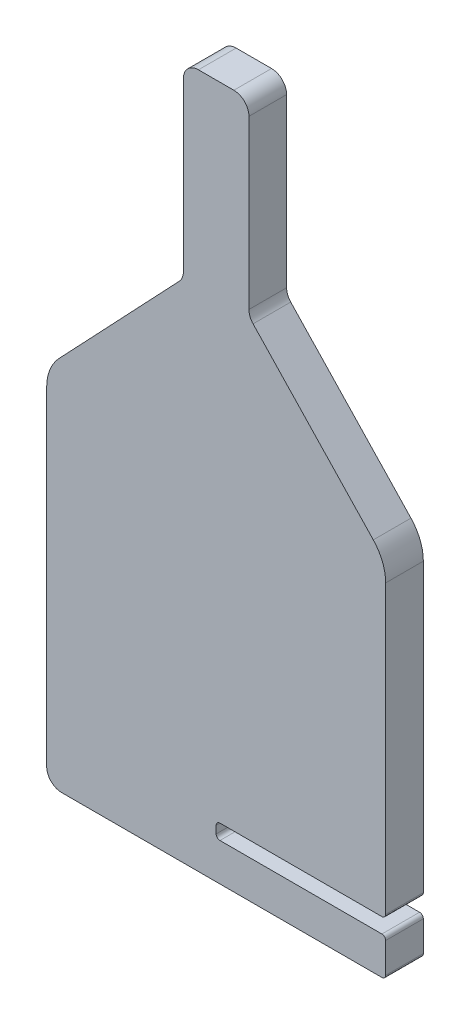
SolidWorks part; units mm, degrees
ref_plane "Alzado" through (0, 0, 0) normal (0, 0, 1) x (1, 0, 0)
ref_plane "Planta" through (0, 0, 0) normal (0, 1, 0) x (1, 0, 0)
ref_plane "Vista lateral" through (0, 0, 0) normal (1, 0, 0) x (0, 0, -1)
sketch "Croquis1" plane through (0, 0, 0) normal (0, 0, 1) x (1, 0, 0)
  line L0 (-4.35, 20) -> (-22.5, 0.8287)
  line L1 (-4.35, 45) -> (4.35, 45)
  line L2 (-22.5, 0.8287) -> (-22.5, -47.1713)
  line L3 (-22.5, -47.1713) -> (22.5, -47.1713)
  line L4 (22.5, 0.8287) -> (22.5, -47.1713)
  line L5 (-4.35, 45) -> (4.35, 45)
  line L6 (-4.35, 45) -> (-4.35, 20)
  line L8 (4.35, 45) -> (4.35, 19.999)
  line L9 (4.35, 19.999) -> (22.5, 0.8287)
  line L10 (0, 72.8664) -> (0, -82.626) construction
  dimension "D1" = 45
  dimension "D2" = 25
  dimension "D3" = 4.35
  dimension "D4" = 22.5
  dimension "D5" = 45
  dimension "D6" = 4.35
  dimension "D7" = 26.3993
  dimension "D8" = 26.4
  dimension "D9" = 48
  dimension "D10" = 48
extrude "Saliente-Extruir1" add sketch "Croquis1" along normal blind 5 contours L6 L0 L2 L3 L4 L9 L8 L1
sketch "Croquis3" plane through (0, 0, 5) normal (0, 0, 1) x (1, 0, 0)
  line L0 (22.5, 0.8287) -> (22.5, -47.1713) construction
  line L1 (22.5, -40.1713) -> (0, -40.1713)
  line L2 (22.5, -40.1713) -> (22.5, -42.1713)
  line L3 (22.5, -42.1713) -> (0, -42.1713)
  line L4 (0, -40.1713) -> (0, -42.1713)
  line L5 (-22.5, -47.1713) -> (22.5, -47.1713) construction
  dimension "D1" = 2
  dimension "D2" = 5
  dimension "D3" = 22.5
extrude "Cortar-Extruir2" cut sketch "Croquis3" against normal up to surface (5 mm away) up to face at (0, 4.6642, 0)
fillet "Redondeo1" radius 2 5 edges at (-22.5, -47.1713, 2.5) (-4.35, 20, 2.5) (-4.35, 45, 2.5) (4.35, 19.999, 2.5) (4.35, 45, 2.5)
fillet "Redondeo2" radius 6 2 edges at (-22.5, 0.8287, 2.5) (22.5, 0.8287, 2.5)
fillet "Redondeo3" radius 0.5 5 edges at (0, -42.1713, 2.5) (0, -40.1713, 2.5) (22.5, -42.1713, 2.5) (22.5, -40.1713, 2.5) (22.5, -47.1713, 2.5)
